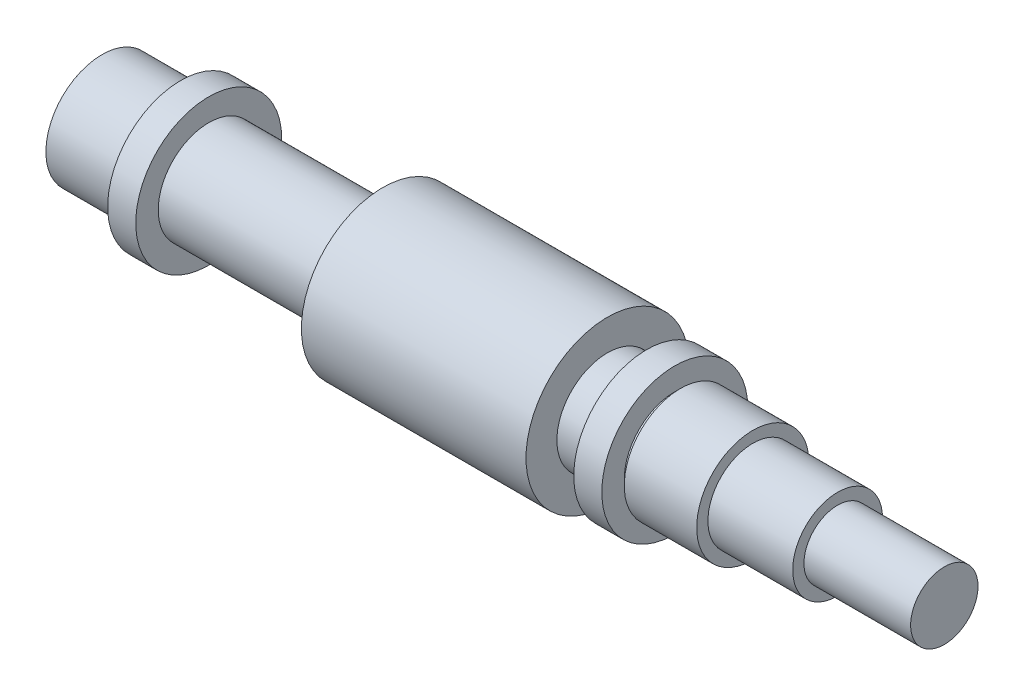
SolidWorks part; units mm, degrees
ref_plane "前视基准面" through (0, 0, 0) normal (0, 0, 1) x (1, 0, 0)
ref_plane "上视基准面" through (0, 0, 0) normal (0, 1, 0) x (1, 0, 0)
ref_plane "右视基准面" through (0, 0, 0) normal (1, 0, 0) x (0, 0, -1)
other "Configuration Table"
sketch "草图1" plane through (0, 0, 0) normal (0, 0, 1) x (1, 0, 0)
  line L0 (0, 0) -> (-22.028, 0) construction
  line L1 (0, 0) -> (0, 10)
  line L2 (0, 10) -> (13, 10)
  line L3 (13, 10) -> (13, 9)
  line L4 (13, 9) -> (14, 9)
  line L5 (14, 9) -> (14, 13)
  line L6 (14, 13) -> (19, 13)
  line L7 (19, 13) -> (19, 9)
  line L8 (19, 9) -> (50, 9)
  line L9 (50, 9) -> (50, 14.5)
  line L10 (50, 14.5) -> (90, 14.5)
  line L11 (90, 14.5) -> (90, 9)
  line L12 (90, 9) -> (97, 9)
  line L13 (97, 9) -> (97, 13)
  line L15 (115.9, 10) -> (115.9, 8)
  line L18 (150, 0) -> (0, 0)
  line L19 (115.9, 8) -> (131, 8)
  line L20 (131, 8) -> (131, 6)
  line L22 (131, 6) -> (150, 6)
  line L23 (150, 6) -> (150, 0)
  line L24 (97, 13) -> (102, 13)
  line L25 (102, 13) -> (102, 9)
  line L26 (102, 9) -> (103, 9)
  line L27 (103, 9) -> (103, 10)
  line L28 (103, 10) -> (115.9, 10)
  dimension "D1" = 150
  dimension "D2" = 1
  dimension "D3" = 1
  dimension "D4" = 14
  dimension "D5" = 20
  dimension "D6" = 26
  dimension "D7" = 18
  dimension "D8" = 18
  dimension "D9" = 1
  dimension "D10" = 8
  dimension "D11" = 19
  dimension "D12" = 34.1
  dimension "D13" = 5
  dimension "D14" = 36
  dimension "D15" = 40
  dimension "D16" = 48
  dimension "D17" = 10
  dimension "D18" = 13
  dimension "D19" = 5
  dimension "D20" = 6
  dimension "D21" = 29
revolve "旋转1" add sketch "草图1" angle 360 about L0
